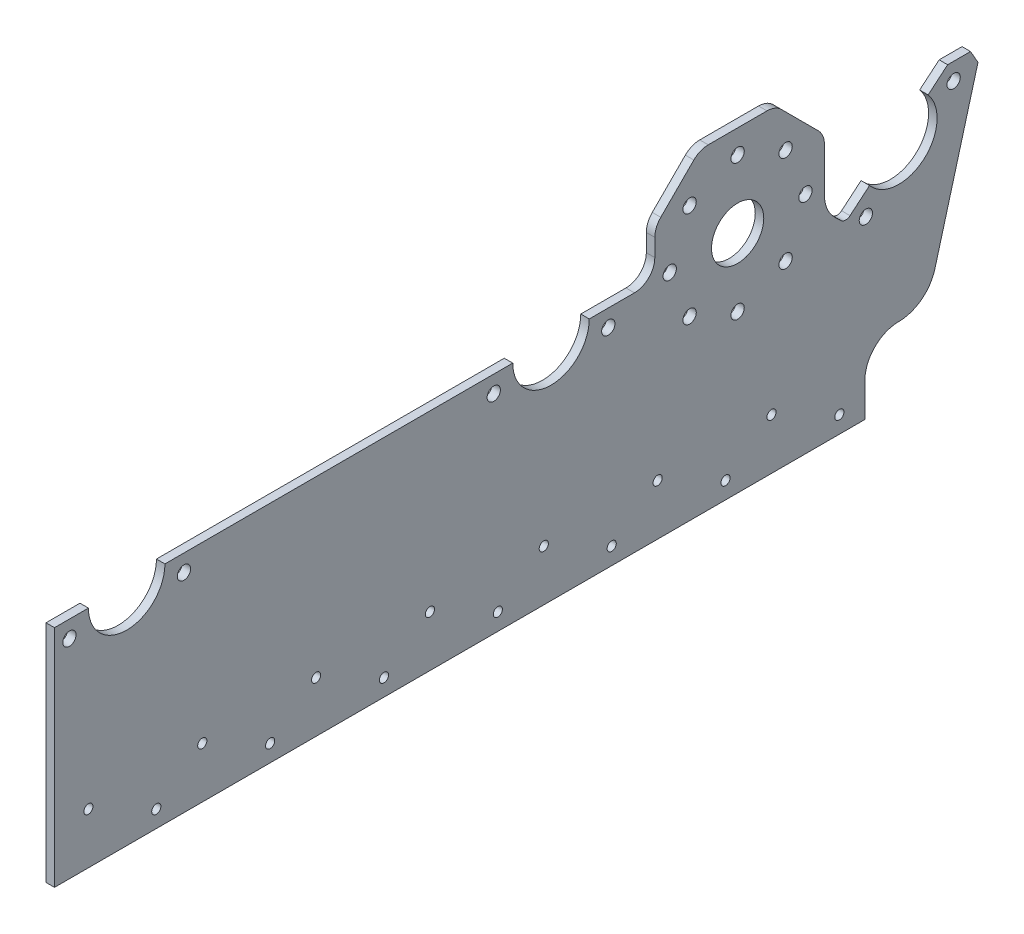
SolidWorks part; units mm, degrees
material "6061 Alloy"
ref_plane "Front Plane" through (0, 0, 0) normal (0, 0, 1) x (1, 0, 0)
ref_plane "Top Plane" through (0, 0, 0) normal (0, 1, 0) x (1, 0, 0)
ref_plane "Right Plane" through (0, 0, 0) normal (1, 0, 0) x (0, 0, -1)
sketch "Sketch1" plane through (0, 0, 0) normal (1, 0, 0) x (0, 0, -1)
  line L0 (-12.7, -12.7) -> (-315.9379, -12.7)
  line L1 (-315.9379, -12.7) -> (-315.9379, 71.4629)
  line L2 (-315.9379, 71.4629) -> (-303.2379, 71.4629)
  line L3 (-274.6121, 71.4629) -> (-144.4625, 71.4629)
  line L5 (10.9643, 80.6631) -> (18.2626, 86.7871)
  line L7 (-315.9379, 12.7) -> (13.4731, 12.7) construction
  line L8 (-12.7, -12.7) -> (-12.7, 0)
  line L9 (0, 12.4079) -> (0, 12.7) construction
  line L10 (13.4731, 22.9772) -> (30.9626, 86.7871)
  line L12 (-10.9643, 62.2627) -> (10.9643, 80.6631) construction
  line L13 (18.2626, 86.7871) -> (30.9626, 86.7871)
  line L14 (-115.8367, 71.4629) -> (-91.313, 71.4629)
  line L15 (-10.9643, 62.2627) -> (-18.2626, 56.1387)
  line L16 (-21.6532, 56.2511) -> (-23.945, 58.4485)
  line L18 (0, 71.4629) -> (-130.1496, 71.4629) construction
  line L19 (-315.9379, 15.875) -> (13.4731, 15.875) construction
  line L20 (-27.8553, 67.6154) -> (-27.8553, 87.307)
  line L21 (-27.8553, 87.307) -> (-46.1742, 105.6259)
  line L22 (-46.1742, 105.6259) -> (-74.4758, 105.6259)
  line L23 (-91.313, 88.7887) -> (-91.313, 71.4629)
  line L25 (-74.4758, 105.6259) -> (-91.313, 88.7887)
  arc A3 (0, 12.7) -> (13.4731, 22.9772) centre (0, 26.67) ccw
  arc A4 (0, 12.7) -> (-12.7, 0) centre (0, 0) ccw
  circle A5 centre (0, 0) radius 12.4079 construction
  arc A6 (-303.2379, 71.4629) -> (-274.6121, 71.4629) centre (-288.925, 71.4629) ccw
  arc A7 (-144.4625, 71.4629) -> (-115.8367, 71.4629) centre (-130.1496, 71.4629) ccw
  arc A8 (-10.9643, 62.2627) -> (10.9643, 80.6631) centre (0, 71.4629) ccw
  arc A9 (-18.2626, 56.1387) -> (-21.6532, 56.2511) centre (-19.8953, 58.0845) cw
  circle A11 centre (-60.325, 71.4629) radius 9.779
  arc A14 (-27.8553, 67.6154) -> (-23.945, 58.4485) centre (-15.1553, 67.6154) ccw
  circle A15 centre (-60.325, 71.4629) radius 25.4 construction
  circle A16 centre (-60.325, 96.8629) radius 2.413
  circle A17 centre (-42.3645, 89.4234) radius 2.413
  circle A18 centre (-34.925, 71.4629) radius 2.413
  circle A19 centre (-42.3645, 53.5024) radius 2.413
  circle A20 centre (-60.325, 46.0629) radius 2.413
  circle A21 centre (-78.2855, 53.5024) radius 2.413
  circle A22 centre (-85.725, 71.4629) radius 2.413
  circle A23 centre (-78.2855, 89.4234) radius 2.413
  point P4 (-164.319, -12.7)
  point P44 (-82.018, 71.4629)
  point P51 (-27.8553, 62.1979)
  point P60 (-60.325, 71.4629)
  dimension "D1" = 25.4
  dimension "D3" = 12.7
  dimension "D5" = 28.6258
  dimension "D6" = 3.175
  dimension "D7" = 13.97
  dimension "D8" = 12.7
  dimension "D10" = 24.8158
  dimension "D13" = 9.5273
  dimension "D14" = 140
  dimension "D15" = 2.54
  dimension "D16" = 50.8
  dimension "D17" = 60.325
  dimension "D18" = 41.275
  dimension "D24" = 3.175
  dimension "D26" = 12.7
  dimension "D19" = 4.826
  dimension "D25" = 6.35
  dimension "D29" = 6.35
  dimension "D20" = 4.6567
  dimension "D30" = 9.779
  dimension "D2" = 0
  dimension "D4" = 12.7
  dimension "D9" = 12.7
  dimension "D11" = 288.925
  dimension "D12" = 288.925
  dimension "D21" = 8
  dimension "D22" = 45
  dimension "D23" = 45
  dimension "D27" = 6.35
  dimension "D28" = 3.175
extrude "Boss-Extrude1" add sketch "Sketch1" along normal blind 3.175
hole_wizard "#10 Clearance Hole1" positions "Sketch2" profile "Sketch3" hole size "#10" standard "ANSI Inch" end condition through all
sketch "Sketch2" plane through (3.175, 0, 0) normal (1, 0, 0) x (0, 0, -1)
  line L0 (-310.3562, 65.1129) -> (-267.4937, 65.1129) construction
  line L2 (-151.5808, 65.1129) -> (-108.7184, 65.1129) construction
  line L4 (-12.3356, 52.8228) -> (20.499, 80.3743) construction
  line L6 (-303.2379, 71.4629) -> (-315.9379, 71.4629) construction
  line L7 (-288.925, 65.1129) -> (-288.925, 71.4629) construction
  line L9 (-130.1496, 71.4629) -> (-130.1496, 65.1129) construction
  line L11 (0, 71.4629) -> (4.0817, 66.5985) construction
  line L14 (18.2626, 86.7871) -> (10.9643, 80.6631) construction
  line L15 (18.2626, 86.7871) -> (10.9643, 80.6631) construction
  point P0 (-310.3562, 65.1129)
  point P2 (-267.4937, 65.1129)
  point P4 (-151.5808, 65.1129)
  point P6 (-108.7184, 65.1129)
  point P8 (-12.3356, 52.8228)
  point P10 (20.499, 80.3743)
  dimension "D1" = 42.8625
  dimension "D2" = 6.35
  dimension "D3" = 6.35
sketch "Sketch3" plane through (3.175, 65.1129, 310.3562) normal (0, 1, 0) x (0, 0, -1)
  line L0 (0, 0) -> (0, 3.175)
  line L1 (0, 3.175) -> (2.4892, 3.175)
  line L2 (2.4892, 3.175) -> (2.4892, 0)
  line L5 (2.4892, 0) -> (0, 0)
  line L11 (0, -6.35) -> (0, 107.95) construction
  dimension "Thru Hole Dia." = 4.9784
  dimension "Thru Hole Depth" = 3.175
hole_wizard "#10 Clearance Hole2" positions "Sketch5" profile "Sketch6" hole size "#10" standard "ANSI Inch"
sketch "Sketch5" plane through (3.175, 0, 0) normal (1, 0, 0) x (0, 0, -1)
  point P0 (-60.325, 96.8629)
  point P3 (-42.3645, 89.4234)
  point P6 (-34.925, 71.4629)
  point P9 (-42.3645, 53.5024)
  point P12 (-60.325, 46.0629)
  point P15 (-78.2855, 53.5024)
  point P18 (-85.725, 71.4629)
  point P21 (-78.2855, 89.4234)
sketch "Sketch6" plane through (3.175, 96.8629, 60.325) normal (0, 1, 0) x (0, 0, -1)
  line L0 (0, 0) -> (0, 4.6707)
  line L1 (0, 4.6707) -> (2.4892, 3.175)
  line L2 (2.4892, 3.175) -> (2.4892, 0)
  line L5 (2.4892, 0) -> (0, 0)
  line L10 (0, 4.6707) -> (-2.4892, 3.175) construction
  line L11 (0, -6.35) -> (0, 107.95) construction
  dimension "Hole Dia." = 4.9784
  dimension "Hole Depth" = 3.175
  dimension "Drill Angle" = 118
chamfer "Chamfer1" distance 5.08 angle 45 1 edges at (1.5875, 86.7871, -30.9626) first distance on face at (1.5875, 54.8821, -22.2179)
fillet "Fillet1" radius 7.62 5 edges at (1.5875, 87.307, 27.8553) (1.5875, 105.6259, 46.1742) (1.5875, 105.6259, 74.4758) (1.5875, 88.7887, 91.313) (1.5875, 71.4629, 91.313)
hole_wizard "1/8 (0.135) Diameter Hole1" positions "Sketch7" profile "Sketch8" hole size "1/8" standard "ANSI Inch"
sketch "Sketch7" plane through (0, 0, 0) normal (-1, 0, 0) x (0, 0, 1)
  line L0 (315.9379, -12.7) -> (12.7, -12.7) construction
  line L1 (12.7, -12.7) -> (12.7, 0) construction
  line L2 (315.9379, 71.4629) -> (315.9379, -12.7) construction
  point P0 (22.2504, -6.35)
  point P2 (47.6504, 6.35)
  point P19 (64.8483, -6.35)
  point P20 (90.2483, 6.35)
  point P21 (107.4462, -6.35)
  point P22 (132.8462, 6.35)
  point P23 (150.0441, -6.35)
  point P24 (175.4441, 6.35)
  point P25 (192.6421, -6.35)
  point P26 (218.0421, 6.35)
  point P27 (235.24, -6.35)
  point P28 (260.64, 6.35)
  point P29 (277.8379, -6.35)
  point P30 (303.2379, 6.35)
  dimension "D1" = 6.35
  dimension "D2" = 25.4
  dimension "D3" = 12.7
  dimension "D4" = 9.5504
  dimension "D6" = 12.7
  dimension "D5" = 7
sketch "Sketch8" plane through (0, -6.35, 22.2504) normal (0, 1, 0) x (0, 0, 1)
  line L0 (0, 0) -> (0, 17.5402)
  line L1 (0, 17.5402) -> (1.7145, 16.51)
  line L2 (1.7145, 16.51) -> (1.7145, 0)
  line L5 (1.7145, 0) -> (0, 0)
  line L10 (0, 17.5402) -> (-1.7145, 16.51) construction
  line L11 (0, -6.35) -> (0, 107.95) construction
  dimension "Hole Dia." = 3.429
  dimension "Hole Depth" = 16.51
  dimension "Drill Angle" = 118
